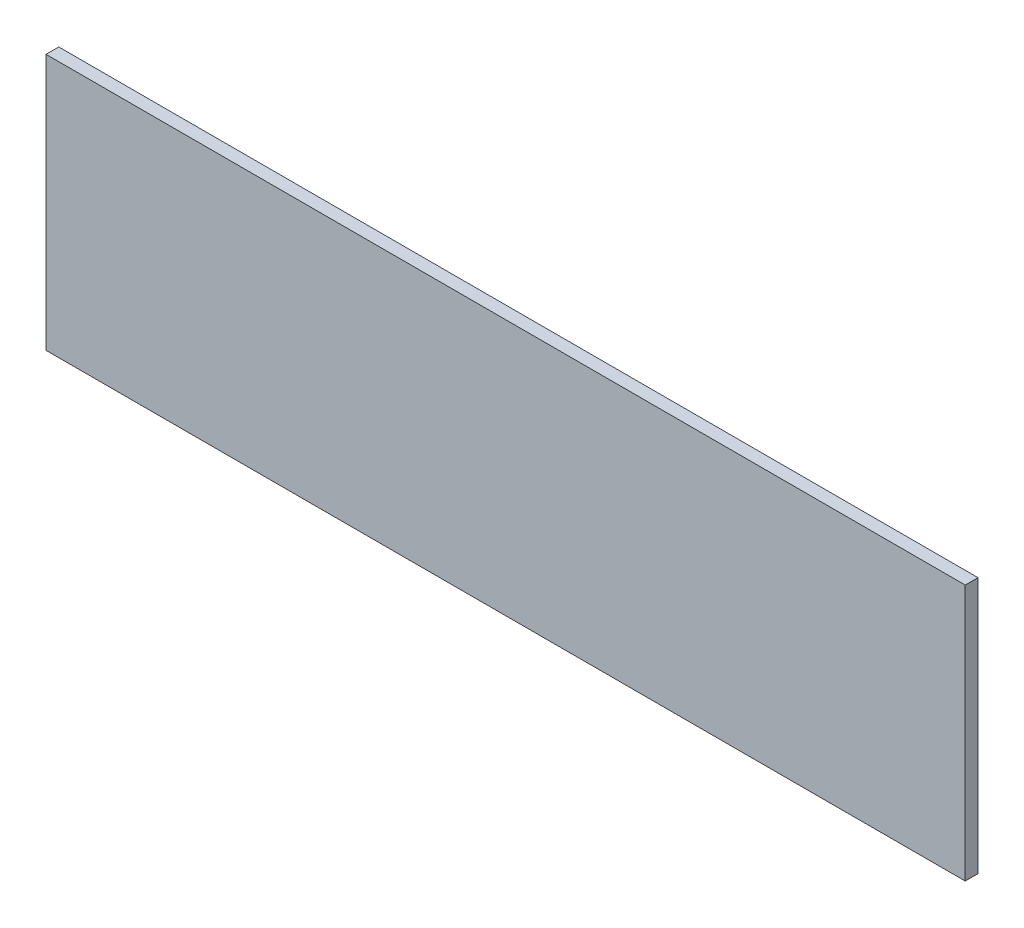
SolidWorks part; units mm, degrees
ref_plane "Front Plane" through (0, 0, 0) normal (0, 0, 1) x (1, 0, 0)
ref_plane "Top Plane" through (0, 0, 0) normal (0, 1, 0) x (1, 0, 0)
ref_plane "Right Plane" through (0, 0, 0) normal (1, 0, 0) x (0, 0, -1)
sketch "Sketch1" plane through (0, 0, 0) normal (0, 0, 1) x (1, 0, 0)
  line L0 (0, 0) -> (0, -63.754)
  line L1 (0, -63.754) -> (228.6, -63.754)
  line L3 (0, 0) -> (228.6, 0)
  line L6 (228.6, 0) -> (228.6, -63.754)
  dimension "D3" = 228.6
  dimension "D5" = 63.754
extrude "Base Extrude" add sketch "Sketch1" along normal blind 3.175
